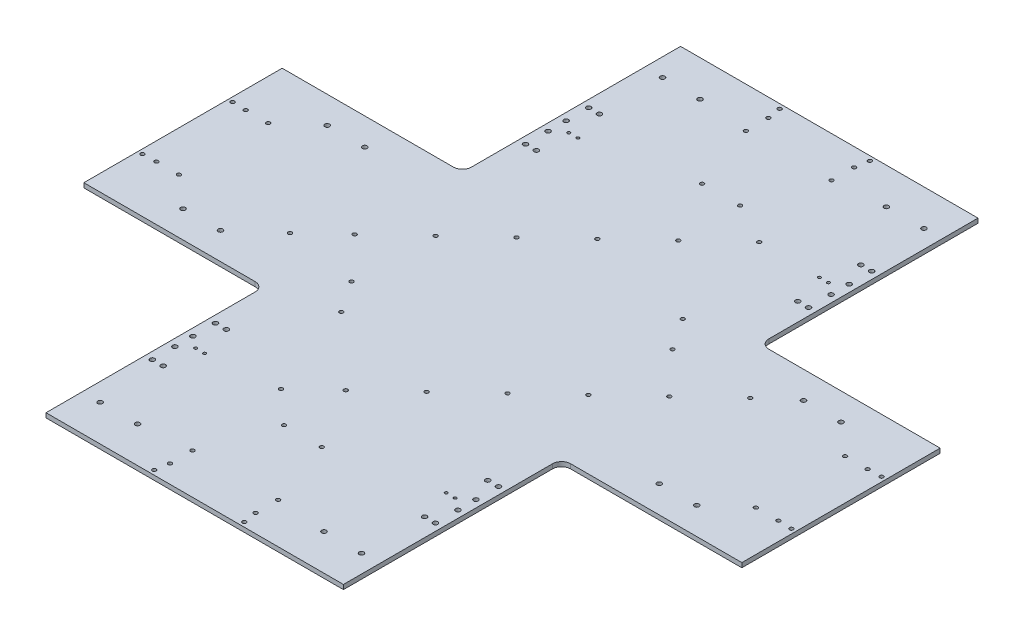
SolidWorks part; units mm, degrees
other "Markup1"
sketch "Sketch8"
material "3.0205 (EN-AW 1200)"
ref_plane "前视基准面" through (0, 0, 0) normal (0, 0, 1) x (1, 0, 0)
ref_plane "上视基准面" through (0, 0, 0) normal (0, 1, 0) x (1, 0, 0)
ref_plane "右视基准面" through (0, 0, 0) normal (1, 0, 0) x (0, 0, -1)
other "Configuration Table"
sketch "Sketch1" plane through (0, 0, 0) normal (0, 1, 0) x (1, 0, 0)
  line L0 (165, 352) -> (-165, 352)
  line L1 (-165, 352) -> (-165, 110)
  line L2 (-165, 110) -> (-365, 110)
  line L5 (-365, 110) -> (-365, -110)
  line L6 (0, 352) -> (0, -66.8675) construction
  line L7 (-365, 0) -> (131.0517, 0) construction
  line L8 (365, 110) -> (365, -110)
  line L11 (165, 110) -> (365, 110)
  line L12 (165, 352) -> (165, 110)
  line L13 (165, -352) -> (165, -110)
  line L14 (165, -110) -> (365, -110)
  line L19 (-165, -110) -> (-365, -110)
  line L20 (-165, -352) -> (-165, -110)
  line L21 (165, -352) -> (-165, -352)
  point P21 (365, 0)
  dimension "D1" = 165
  dimension "D2" = 200
  dimension "D3" = 110
  dimension "D4" = 242
extrude "Boss-Extrude1" add sketch "Sketch1" along normal blind 5
sketch "Sketch2" plane through (0, 5, 0) normal (0, 1, 0) x (1, 0, 0)
  line L3 (365, -110) -> (365, 110) construction
  line L4 (-56.7455, 0) -> (47.5165, 0) construction
  line L5 (0, 54.7142) -> (0, -64.2255) construction
  line L7 (165, 352) -> (-165, 352) construction
  circle A0 centre (345, 49.5) radius 2.125
  circle A1 centre (320, 49.5) radius 2.125
  circle A7 centre (320, -49.5) radius 2.125
  circle A8 centre (345, -49.5) radius 2.125
  circle A9 centre (-345, -49.5) radius 2.125
  circle A10 centre (-320, -49.5) radius 2.125
  circle A13 centre (-320, 49.5) radius 2.125
  circle A14 centre (-345, 49.5) radius 2.125
  circle A15 centre (47.5, 332) radius 2.125
  circle A16 centre (47.5, 307) radius 2.125
  circle A17 centre (-47.5, 307) radius 2.125
  circle A18 centre (-47.5, 332) radius 2.125
  circle A19 centre (-47.5, -332) radius 2.125
  circle A20 centre (-47.5, -307) radius 2.125
  circle A21 centre (47.5, -307) radius 2.125
  circle A22 centre (47.5, -332) radius 2.125
  dimension "D3" = 49.5
  dimension "D5" = 4.25
  dimension "D7" = 4.25
  dimension "D9" = 4.25
  dimension "D10" = 4.25
  dimension "D2" = 47.5
  dimension "D4" = 25
  dimension "D6" = 20
  dimension "20" = 20
  dimension "D13" = 25
extrude "Cut-Extrude1" cut sketch "Sketch2" against normal blind 3
sketch "Sketch4" plane through (0, 5, 0) normal (0, 1, 0) x (1, 0, 0)
  line L0 (-165, 352) -> (-165, 110) construction
  line L1 (165, 352) -> (-165, 352) construction
  line L2 (0, 46.9886) -> (0, -40.2904) construction
  line L3 (-35.103, 0) -> (92.4951, 0) construction
  line L5 (165, -352) -> (165, -110) construction
  circle A0 centre (-157, 172) radius 2.6
  circle A1 centre (-145, 172) radius 2.6
  circle A2 centre (-157, 197) radius 2.6
  circle A3 centre (-157, 217) radius 2.6
  circle A4 centre (-157, 242) radius 2.6
  circle A5 centre (-145, 242) radius 2.6
  circle A6 centre (145, 242) radius 2.6
  circle A7 centre (157, 242) radius 2.6
  circle A8 centre (157, 217) radius 2.6
  circle A9 centre (157, 197) radius 2.6
  circle A10 centre (145, 172) radius 2.6
  circle A11 centre (157, 172) radius 2.6
  circle A12 centre (157, -172) radius 2.6
  circle A13 centre (145, -172) radius 2.6
  circle A14 centre (157, -197) radius 2.6
  circle A15 centre (157, -217) radius 2.6
  circle A16 centre (157, -242) radius 2.6
  circle A17 centre (145, -242) radius 2.6
  circle A18 centre (-145, -242) radius 2.6
  circle A19 centre (-157, -242) radius 2.6
  circle A20 centre (-157, -217) radius 2.6
  circle A21 centre (-157, -197) radius 2.6
  circle A22 centre (-145, -172) radius 2.6
  circle A23 centre (-157, -172) radius 2.6
  circle A24 centre (144, -207) radius 1.6
  circle A25 centre (-144, -207) radius 1.6
  circle A26 centre (144, 207) radius 1.6
  circle A27 centre (-144, 207) radius 1.6
  circle A28 centre (134, -207) radius 1.6
  circle A29 centre (-134, -207) radius 1.6
  circle A30 centre (134, 207) radius 1.6
  circle A31 centre (-134, 207) radius 1.6
  dimension "D3" = 5.2
  dimension "D4" = 5.2
  dimension "D5" = 8
  dimension "D6" = 8
  dimension "D9" = 5.2
  dimension "D10" = 5.2
  dimension "D11" = 5.2
  dimension "D12" = 5.2
  dimension "D19" = 3.2
  dimension "D20" = 21
  dimension "D21" = 10
  dimension "D22" = 3.2
  dimension "D23" = 10
  dimension "D1" = 8
  dimension "D2" = 20
  dimension "D7" = 8
  dimension "D8" = 20
  dimension "D13" = 25
  dimension "D14" = 20
  dimension "D15" = 25
  dimension "D16" = 25
  dimension "D17" = 110
  dimension "D18" = 0
extrude "Cut-Extrude3" cut sketch "Sketch4" against normal blind 10
sketch "Sketch5" plane through (0, 5, 0) normal (0, 1, 0) x (1, 0, 0)
  line L0 (165, 352) -> (-165, 352) construction
  line L5 (-46.9195, 0) -> (66.6223, 0) construction
  line L6 (0, 59.0569) -> (0, -54.4849) construction
  line L10 (-365, 110) -> (-365, -110) construction
  circle A0 centre (-50, 347) radius 2.125
  circle A1 centre (50, 347) radius 2.125
  circle A2 centre (50, -347) radius 2.125
  circle A3 centre (-50, -347) radius 2.125
  circle A4 centre (-360, 50) radius 2.125
  circle A5 centre (-360, -50) radius 2.125
  circle A6 centre (360, -50) radius 2.125
  circle A7 centre (360, 50) radius 2.125
  dimension "D1" = 4.25
  dimension "D2" = 4.25
  dimension "D3" = 50
  dimension "D6" = 4.25
  dimension "D7" = 4.25
  dimension "5" = 5
  dimension "D4" = 50
  dimension "D5" = 50
  dimension "D8" = 50
  dimension "D9" = 5
  dimension "D10" = 5
extrude "Cut-Extrude4" cut sketch "Sketch5" against normal blind 10
fillet "Fillet1" radius 10 4 edges at (-165, 2.5, -110) (-165, 2.5, 110) (165, 2.5, 110) (165, 2.5, -110)
sketch "Sketch6" plane through (0, 5, 0) normal (0, 1, 0) x (1, 0, 0)
  line L0 (165, 352) -> (-165, 352) construction
  line L1 (-165, 352) -> (-165, 120) construction
  line L3 (0, 50.3702) -> (0, -42.7646) construction
  line L4 (-54.8568, 0) -> (91.2004, 0) construction
  line L5 (365, 110) -> (175, 110) construction
  line L6 (365, -110) -> (365, 110) construction
  circle A0 centre (-145, 312) radius 2.6
  circle A1 centre (-103.4, 312) radius 2.6
  circle A4 centre (103.4, 312) radius 2.6
  circle A5 centre (145, 312) radius 2.6
  circle A6 centre (145, -312) radius 2.6
  circle A7 centre (103.4, -312) radius 2.6
  circle A8 centre (-103.4, -312) radius 2.6
  circle A9 centre (-145, -312) radius 2.6
  circle A10 centre (243.4, 80) radius 2.6
  circle A11 centre (285, 80) radius 2.6
  circle A12 centre (285, -80) radius 2.6
  circle A13 centre (243.4, -80) radius 2.6
  circle A14 centre (-243.4, -80) radius 2.6
  circle A15 centre (-285, -80) radius 2.6
  circle A16 centre (-285, 80) radius 2.6
  circle A17 centre (-243.4, 80) radius 2.6
  dimension "D1" = 5.2
  dimension "D2" = 5.2
  dimension "D3" = 5.2
  dimension "D4" = 5.2
  dimension "D5" = 40
  dimension "D8" = 30
  dimension "D6" = 20
  dimension "D7" = 41.6
  dimension "D9" = 80
  dimension "D10" = 41.6
extrude "Cut-Extrude5" cut sketch "Sketch6" against normal blind 10
sketch "Sketch7" plane through (0, 5, 0) normal (0, 1, 0) x (1, 0, 0)
  line L0 (164.5832, 153.9982) -> (-155.4181, -145.4226) construction
  line L1 (165, 299.5544) -> (-272.7048, -110) construction
  line L2 (165, 120) -> (165, 352) construction
  line L3 (-365, -110) -> (-175, -110) construction
  line L4 (272.7048, 110) -> (-165, -299.5544) construction
  line L5 (365, 110) -> (175, 110) construction
  line L6 (-165, -120) -> (-165, -352) construction
  line L7 (-268.9942, -53.3124) -> (-51.1439, -286.1364) construction
  line L8 (84.7791, 253.9237) -> (328.5288, -6.5799) construction
  line L9 (-72.423, 77.401) -> (72.423, -77.401) construction
  line L11 (-380.0049, -355.5654) -> (380.0049, -355.5654) construction
  line L12 (-380.0049, -355.5654) -> (-380.0049, 355.5654) construction
  line L13 (-380.0049, 355.5654) -> (380.0049, 355.5654) construction
  line L14 (380.0049, -355.5654) -> (380.0049, 355.5654) construction
  line L15 (-380.0049, -355.5654) -> (380.0049, 355.5654) construction
  line L16 (-380.0049, 355.5654) -> (380.0049, -355.5654) construction
  circle A4 centre (-72.423, 77.401) radius 2.125
  circle A5 centre (-26.0555, 120.7864) radius 2.125
  circle A6 centre (20.3121, 164.1719) radius 2.125
  circle A7 centre (66.6796, 207.5574) radius 2.125
  circle A8 centre (-118.7906, 34.0155) radius 2.125
  circle A9 centre (-165.1581, -9.37) radius 2.125
  circle A10 centre (-202.2522, -44.0784) radius 2.125
  circle A11 centre (-57.4061, -198.8803) radius 2.125
  circle A12 centre (-20.3121, -164.1719) radius 2.125
  circle A13 centre (26.0555, -120.7864) radius 2.125
  circle A14 centre (211.5257, 52.7555) radius 2.125
  circle A15 centre (165.1581, 9.37) radius 2.125
  circle A16 centre (118.7906, -34.0155) radius 2.125
  circle A17 centre (72.423, -77.401) radius 2.125
  point P53 (0, 0)
  dimension "D6" = 4.25
  dimension "D7" = 4.25
  dimension "D8" = 4.25
  dimension "D9" = 4.25
  dimension "D10" = 4.25
  dimension "D11" = 4.25
  dimension "D12" = 4.25
  dimension "D1" = 106
  dimension "D3" = 20
  dimension "D4" = 20
  dimension "D5" = 0
  dimension "D13" = 63.5
  dimension "D14" = 63.5
  dimension "D15" = 50.8
  dimension "D16" = 63.5
  dimension "D17" = 63.5
  dimension "D18" = 63.5
extrude "Cut-Extrude6" cut sketch "Sketch7" against normal blind 10
sketch "Sketch9" plane through (0, 5, 0) normal (0, 1, 0) x (1, 0, 0)
  line L0 (167.9289, 112.9289) -> (-167.9289, -112.9289) construction
  line L1 (80.349, 117.7232) -> (149.9169, 14.2734) construction
  line L2 (-142.2885, -25.6171) -> (-87.1446, -107.6179) construction
  line L3 (0, 45.0584) -> (0, -52.9183) construction
  line L4 (-44.6513, 0) -> (48.0404, 0) construction
  line L5 (165, 352) -> (-165, 352) construction
  arc A0 (165, 120) -> (175, 110) centre (175, 120) ccw construction
  arc A1 (-165, -120) -> (-175, -110) centre (-175, -120) ccw construction
  circle A2 centre (-121.5605, -56.4403) radius 2.1
  circle A3 centre (-98.123, -91.2926) radius 2.1
  circle A4 centre (98.123, 91.2926) radius 2.1
  circle A5 centre (121.5605, 56.4403) radius 2.1
  circle A7 centre (21, 232) radius 2.1
  circle A8 centre (-21, 232) radius 2.1
  circle A9 centre (-21, -232) radius 2.1
  circle A10 centre (21, -232) radius 2.1
  dimension "D3" = 4.2
  dimension "D4" = 4.2
  dimension "D5" = 4.2
  dimension "D6" = 4.2
  dimension "D11" = 120
  dimension "D12" = 4.2
  dimension "D1" = 70
  dimension "D2" = 70
  dimension "D7" = 21
  dimension "D8" = 21
  dimension "D9" = 21
  dimension "D10" = 21
  dimension "D13" = 21
extrude "Cut-Extrude7" cut sketch "Sketch9" against normal blind 10
